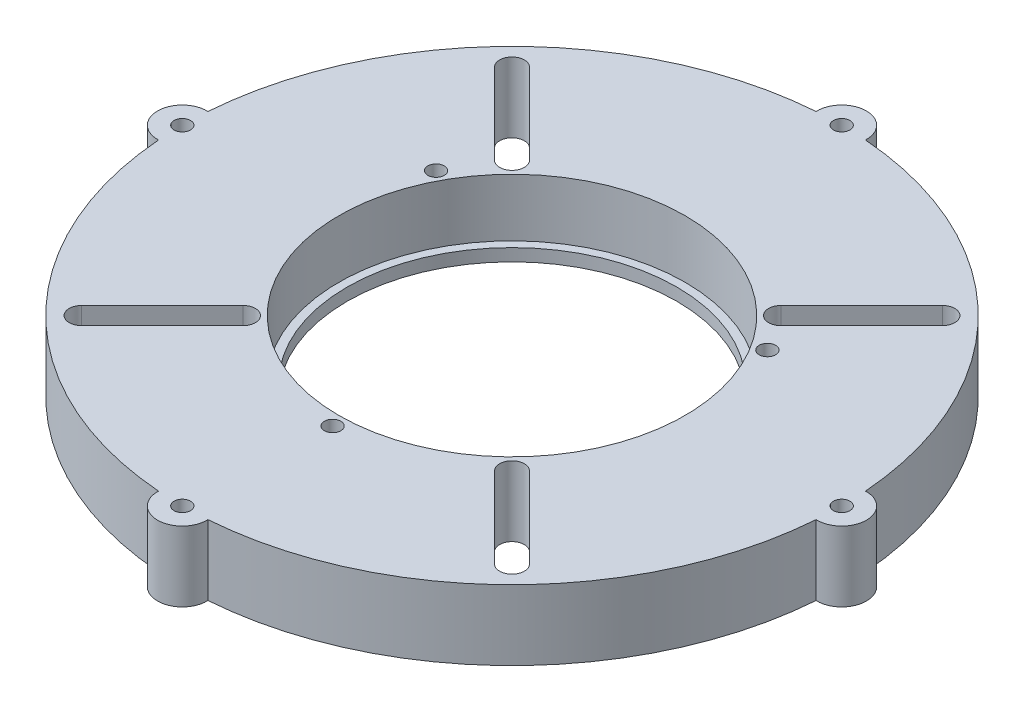
SolidWorks part; units mm, degrees
material "7075-T6 (SN)"
ref_plane "Front Plane" through (0, 0, 0) normal (0, 0, 1) x (1, 0, 0)
ref_plane "Top Plane" through (0, 0, 0) normal (0, 1, 0) x (1, 0, 0)
ref_plane "Right Plane" through (0, 0, 0) normal (1, 0, 0) x (0, 0, -1)
sketch "Sketch1" plane through (0, 0, 0) normal (0, 1, 0) x (1, 0, 0)
  circle A0 centre (0, 0) radius 20
  circle A1 centre (0, 0) radius 40
extrude "Boss-Extrude1" add sketch "Sketch1" along normal blind 8.5 contours A1 | A0
sketch "Sketch2" plane through (0, 8.5, 0) normal (0, 1, 0) x (1, 0, 0)
  circle A0 centre (40, 0) radius 3
  circle A1 centre (40, 0) radius 1
extrude "Cut-Extrude2" cut sketch "Sketch2" against normal through all contours A1
extrude "Boss-Extrude3" add sketch "Sketch2<6>" against normal blind 8.5
sketch "Sketch2<6>" plane through (0, 8.5, 0) normal (0, 1, 0) x (1, 0, 0) same geometry as "Sketch2"
pattern_circular "CirPattern1" count 4 over 360 about axis through (0, 8.5, 0) along (0, 1, 0) of "Cut-Extrude2", "Boss-Extrude3"
sketch "Sketch4" plane through (0, 8.5, 0) normal (0, 1, 0) x (1, 0, 0)
  line L0 (-26.1099, -26.1099) -> (-16.3165, -16.3165) construction
  line L1 (-27.1706, -25.0493) -> (-17.3771, -15.2558)
  line L2 (-25.0493, -27.1706) -> (-15.2558, -17.3771)
  line L3 (-21.2132, -21.2132) -> (0, 0) construction
  arc A0 (-27.1706, -25.0493) -> (-25.0493, -27.1706) centre (-26.1099, -26.1099) ccw
  arc A1 (-15.2558, -17.3771) -> (-17.3771, -15.2558) centre (-16.3165, -16.3165) ccw
  circle A2 centre (0, 0) radius 20 construction
  point P2 (-21.2132, -21.2132)
  dimension "D1" = 13.85
  dimension "D2" = 1.5
  dimension "D3" = 23.075
extrude "Cut-Extrude4" cut sketch "Sketch4" against normal through all
pattern_circular "CirPattern3" count 4 over 360 about axis through (0, 8.5, 0) along (0, 1, 0) of "Cut-Extrude4"
sketch "Sketch7" plane through (0, 8.5, 0) normal (0, 1, 0) x (1, 0, 0)
  circle A0 centre (0, 0) radius 21
extrude "Cut-Extrude5" cut sketch "Sketch7" against normal blind 7
sketch "Sketch8" plane through (0, 8.5, 0) normal (0, 1, 0) x (1, 0, 0)
  circle A0 centre (0.7201, -22.4885) radius 1
  circle A1 centre (19.1156, 11.8678) radius 1
  circle A2 centre (-19.8356, 10.6207) radius 1
extrude "Outer_Retainer_M2_Tapped_Envelope" cut sketch "Sketch8" against normal blind 4.3
sketch "Sketch9" plane through (0, 0, 0) normal (0, -1, 0) x (1, 0, 0)
  circle A0 centre (27.7164, 11.4805) radius 1
  circle A1 centre (-11.4805, 27.7164) radius 1
  circle A2 centre (-27.7164, -11.4805) radius 1
  circle A3 centre (11.4805, -27.7164) radius 1
extrude "RevB_Oldham_Four_M2_Blind_Thread_Major" cut sketch "Sketch9" against normal blind 5.8
sketch "Sketch10" plane through (0, 0, 0) normal (0, -1, 0) x (1, 0, 0)
  circle A0 centre (27.7164, 11.4805) radius 1.51
  circle A1 centre (-11.4805, 27.7164) radius 1.51
  circle A2 centre (-27.7164, -11.4805) radius 1.51
  circle A3 centre (11.4805, -27.7164) radius 1.51
extrude "RevB_Oldham_Four_D3p02_Pilot_Pockets" cut sketch "Sketch10" against normal blind 1.1
